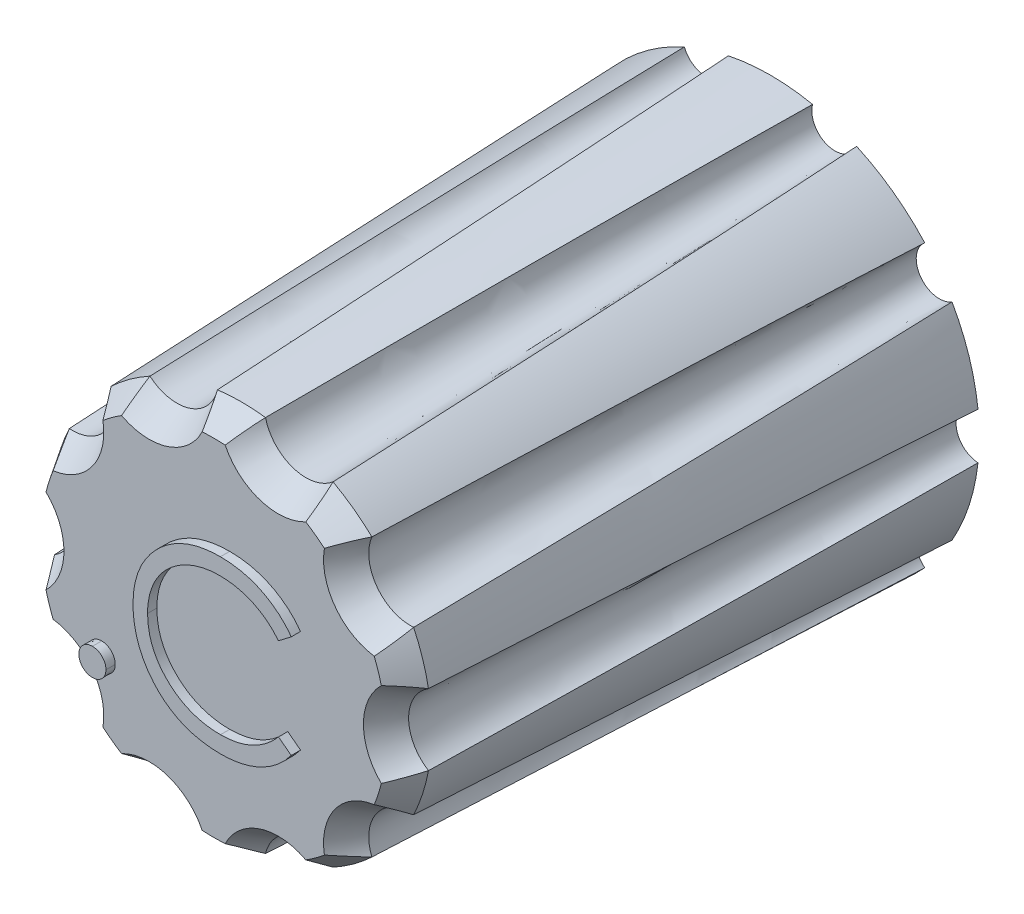
SolidWorks part; units mm, degrees
note: The reader was unsure of these and kept them because the rebuilt part matched: shared geometry of "Esquisse5<2>".
ref_plane "Plan de face" through (0, 0, 0) normal (0, 0, 1) x (1, 0, 0)
ref_plane "Plan de dessus" through (0, 0, 0) normal (0, 1, 0) x (1, 0, 0)
ref_plane "Plan de droite" through (0, 0, 0) normal (1, 0, 0) x (0, 0, -1)
sketch "Esquisse1" plane through (0, 0, 0) normal (0, 0, 1) x (1, 0, 0)
  line L0 (-13.0824, 0) -> (17.5938, 0) construction
  circle A0 centre (0, 0) radius 4.5
  circle A1 centre (-4.5, 0) radius 0.5
  circle A2 centre (-3.6406, 2.645) radius 0.5
  circle A3 centre (-1.3906, 4.2798) radius 0.5
  circle A4 centre (1.3906, 4.2798) radius 0.5
  circle A5 centre (3.6406, 2.645) radius 0.5
  circle A6 centre (4.5, 0) radius 0.5
  circle A7 centre (3.6406, -2.645) radius 0.5
  circle A8 centre (1.3906, -4.2798) radius 0.5
  circle A9 centre (-1.3906, -4.2798) radius 0.5
  circle A10 centre (-3.6406, -2.645) radius 0.5
  point P35 (0, 0)
  dimension "D1" = 9
  dimension "D2" = 1
  dimension "D3" = 10
extrude "Boss.-Extru.1" add sketch "Esquisse1" along normal blind 12 draft 2
chamfer "Chanfrein2" distance 0.6 angle 30 20 edges at (-3.8812, 1.2611, 12) (-2.8971, 2.1048, 12) (-2.3987, 3.3016, 12) (-1.1066, 3.4057, 12) (0, 4.081, 12) (1.1066, 3.4057, 12) (2.3987, 3.3016, 12) (2.8971, 2.1048, 12) (3.8812, 1.2611, 12) (3.581, 0, 12) (3.8812, -1.2611, 12) (2.8971, -2.1048, 12) (2.3987, -3.3016, 12) (1.1066, -3.4057, 12) (0, -4.081, 12) (-1.1066, -3.4057, 12) (-2.3987, -3.3016, 12) (-2.8971, -2.1048, 12) (-3.8812, -1.2611, 12) (-3.581, 0, 12)
sketch "Esquisse2" plane through (0, 0, 0) normal (0, 0, -1) x (-1, 0, 0)
  line L0 (2.6552, -1.6) -> (-2.6552, -1.6)
  circle A0 centre (0, 0) radius 3.1
  dimension "D1" = 6.2
  dimension "D2" = 1.6
extrude "Enlèv. mat.-Extru.1" cut sketch "Esquisse2" against normal blind 10 contours L0 A0
sketch "Esquisse4" plane through (0, 0, 0) normal (0, 0, -1) x (-1, 0, 0)
  line L0 (2.6552, -1.6) -> (-2.6552, -1.6) construction
  circle A0 centre (-2.6552, -1.6) radius 0.2
  circle A1 centre (2.5981, -1.6) radius 0.2
  dimension "D1" = 0.4
  dimension "D2" = 0.4
extrude "Enlèv. mat.-Extru.4" cut sketch "Esquisse4" against normal blind 10
sketch "Esquisse5" plane through (0, 0, 12) normal (0, 0, 1) x (1, 0, 0)
  line L0 (-3.1089, -1.8053) -> (3.1456, -1.8053) construction
  text T0 ".C"
extrude "Enlèv. mat.-Extru.5" cut sketch "Esquisse5" against normal blind 0.2
extrude "Boss.-Extru.2" add sketch "Esquisse5<2>" along normal blind 0.2 separate body
sketch "Esquisse5<2>" plane through (0, 0, 12) normal (0, 0, 1) x (1, 0, 0) same geometry as "Esquisse5"
chamfer "Chanfrein3" distance 0.2 angle 45 1 edges at (0.0286, -1.6, 0)
